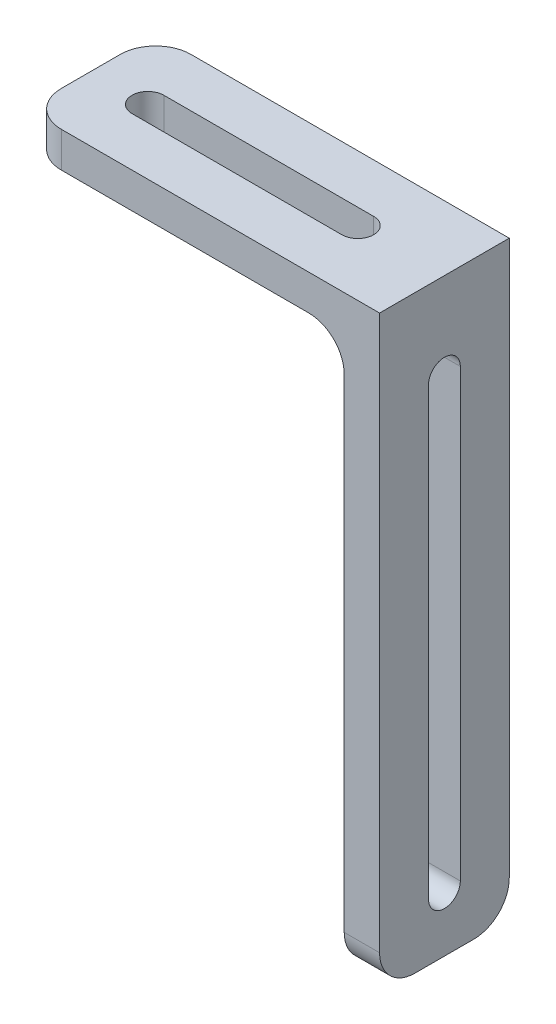
SolidWorks part; units mm, degrees
ref_plane "Front Plane" through (0, 0, 0) normal (0, 0, 1) x (1, 0, 0)
ref_plane "Top Plane" through (0, 0, 0) normal (0, 1, 0) x (1, 0, 0)
ref_plane "Right Plane" through (0, 0, 0) normal (1, 0, 0) x (0, 0, -1)
sketch "Sketch1" plane through (0, 0, 0) normal (0, 0, 1) x (1, 0, 0)
  line L0 (0, 0) -> (3, 0)
  line L1 (3, 0) -> (3, 50)
  line L2 (3, 50) -> (-27, 50)
  line L3 (-27, 50) -> (-27, 47)
  line L4 (-27, 47) -> (0, 47)
  line L5 (0, 47) -> (0, 0)
  dimension "D1" = 27
  dimension "D2" = 50
  dimension "D3" = 3
  dimension "D4" = 3
extrude "Boss-Extrude1" add sketch "Sketch1" along normal blind 11
sketch "Sketch6" plane through (3, 0, 0) normal (1, 0, 0) x (0, 0, -1)
  line L0 (-5.5, 50) -> (-5.5, 0) construction
  line L1 (-11, 50) -> (0, 50) construction
  line L2 (-11, 0) -> (0, 0) construction
  line L3 (-5.5, 42.65) -> (-5.5, 4.85) construction
  line L4 (-4.15, 42.65) -> (-4.15, 4.85)
  line L5 (-6.85, 42.65) -> (-6.85, 4.85)
  arc A0 (-4.15, 42.65) -> (-6.85, 42.65) centre (-5.5, 42.65) ccw
  arc A1 (-6.85, 4.85) -> (-4.15, 4.85) centre (-5.5, 4.85) ccw
  point P8 (-5.5, 23.75)
  point P13 (-5.5, 44)
  point P14 (-5.5, 3.5)
  dimension "D1" = 2.7
  dimension "D2" = 6
  dimension "D3" = 3.5
  dimension "D4" = 40.5
extrude "Cut-Extrude1" cut sketch "Sketch6" against normal through all
sketch "Sketch7" plane through (0, 50, 0) normal (0, 1, 0) x (1, 0, 0)
  line L0 (-27, -5.5) -> (3, -5.5) construction
  line L1 (-27, -11) -> (-27, 0) construction
  line L2 (3, -11) -> (3, 0) construction
  line L3 (-22.15, -5.5) -> (-4.35, -5.5) construction
  line L4 (-22.15, -4.15) -> (-4.35, -4.15)
  line L5 (-22.15, -6.85) -> (-4.35, -6.85)
  arc A0 (-22.15, -4.15) -> (-22.15, -6.85) centre (-22.15, -5.5) ccw
  arc A1 (-4.35, -6.85) -> (-4.35, -4.15) centre (-4.35, -5.5) ccw
  point P8 (-13.25, -5.5)
  point P13 (-23.5, -5.5)
  point P14 (-3, -5.5)
  dimension "D2" = 6
  dimension "D1" = 3.5
  dimension "D3" = 2.7
  dimension "D4" = 20.5
extrude "Cut-Extrude2" cut sketch "Sketch7" against normal through all contours L4 A1 L5 A0
fillet "Fillet1" radius 3 1 edges at (0, 47, 5.5)
fillet "Fillet2" radius 3 4 edges at (1.5, 0, 0) (1.5, 0, 11) (-27, 48.5, 11) (-27, 48.5, 0)
sketch "Sketch8" plane through (3, 0, 0) normal (1, 0, 0) x (0, 0, -1)
  line L0 (-5.5, 44) -> (-5.5, 3.5) construction
  arc A0 (-6.85, 4.85) -> (-4.15, 4.85) centre (-5.5, 4.85) ccw construction
